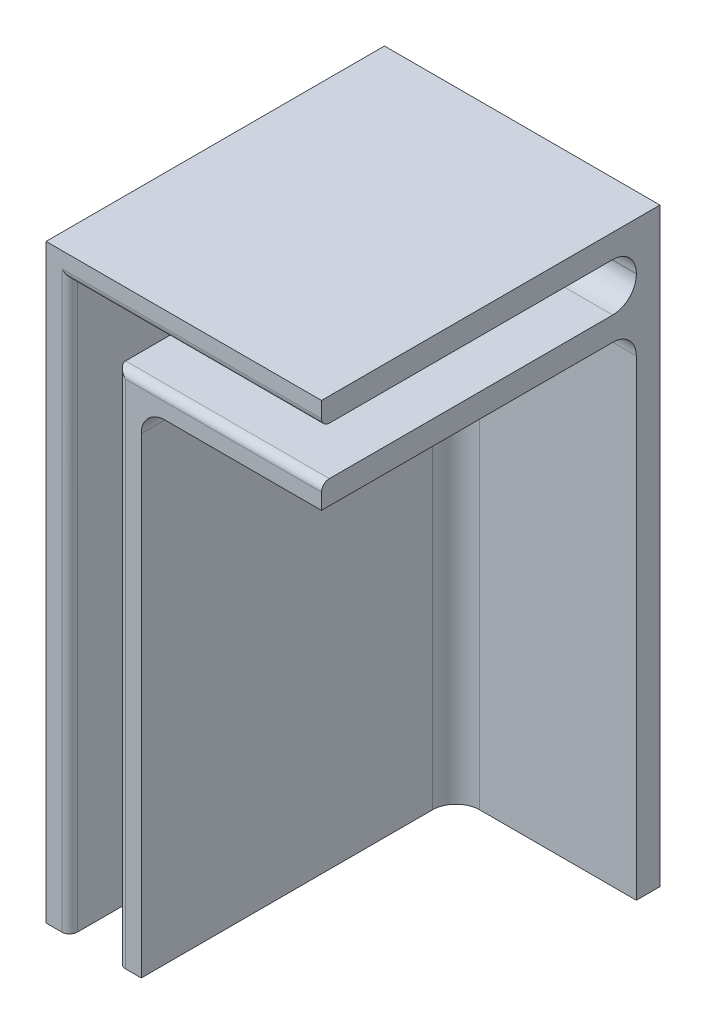
SolidWorks part; units mm, degrees
ref_plane "Front" through (0, 0, 0) normal (0, 0, 1) x (1, 0, 0)
ref_plane "Top" through (0, 0, 0) normal (0, 1, 0) x (1, 0, 0)
ref_plane "Right" through (0, 0, 0) normal (1, 0, 0) x (0, 0, -1)
sketch "Sketch1" plane through (0, 0, 0) normal (0, 0, 1) x (1, 0, 0)
  line L5 (0, 0) -> (35, 0)
  line L6 (0, 0) -> (0, 75)
  line L7 (0, 75) -> (35, 75)
  line L8 (35, 0) -> (35, 75)
  dimension "D1" = 75
  dimension "D2" = 35
extrude "Boss-Extrude1" add sketch "Sketch1" along normal blind 3
sketch "Sketch2" plane through (0, 0, 3) normal (0, 0, 1) x (1, 0, 0)
  line L0 (35, 65.9) -> (9.1, 65.9)
  line L5 (35, 0) -> (35, 75) construction
  line L10 (9.1, 65.9) -> (9.1, 0)
  line L15 (0, 75) -> (35, 75)
  line L16 (0, 75) -> (0, 49)
  line L17 (3, 72) -> (35, 72)
  line L18 (35, 75) -> (35, 72)
  line L19 (0, 0) -> (35, 0) construction
  line L21 (0, 49) -> (0, 0)
  line L22 (0, 0) -> (3, 0)
  line L23 (3, 72) -> (3, 0)
  line L24 (9.1, 0) -> (12.1, 0)
  line L25 (35, 62.9) -> (12.1, 62.9)
  line L26 (35, 62.9) -> (35, 65.9)
  line L32 (12.1, 62.9) -> (12.1, 0)
  dimension "D1" = 3
  dimension "D2" = 6.1
  dimension "D3" = 6.1
extrude "Boss-Extrude2" add sketch "Sketch2" along normal blind 40
fillet "Fillet1" radius 3 7 edges at (22.05, 65.9, 3) (19, 72, 3) (12.1, 62.9, 23) (23.55, 62.9, 3) (12.1, 31.45, 3) (9.1, 32.95, 3) (3, 36, 3)
fillet "Fillet2" radius 1 4 edges at (3, 36, 43) (19, 72, 43) (22.05, 65.9, 43) (9.1, 32.95, 43)
